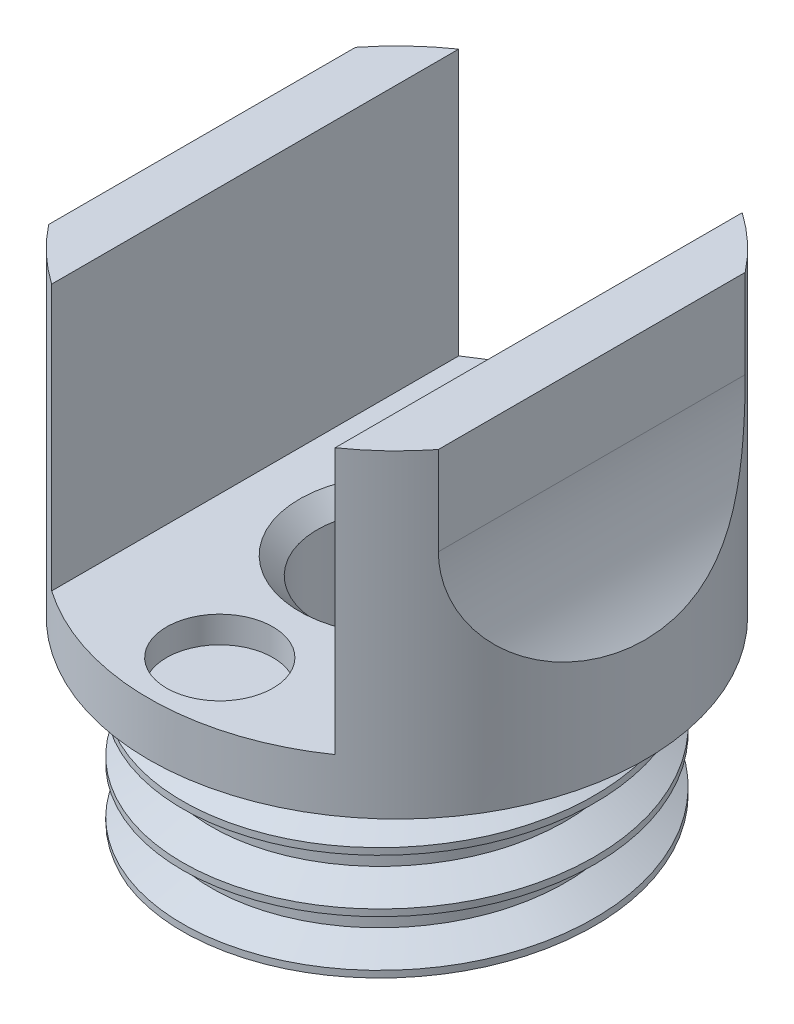
SolidWorks part; units mm, degrees
ref_plane "前视基准面" through (0, 0, 0) normal (0, 0, 1) x (1, 0, 0)
ref_plane "上视基准面" through (0, 0, 0) normal (0, 1, 0) x (1, 0, 0)
ref_plane "右视基准面" through (0, 0, 0) normal (1, 0, 0) x (0, 0, -1)
other "Configuration Table"
sketch "草图1" plane through (0, 0, 0) normal (0, 1, 0) x (1, 0, 0)
  circle A0 centre (0, 0) radius 10
  dimension "D1" = 20
extrude "凸台-拉伸1" add sketch "草图1" along normal blind 10
sketch "草图2" plane through (0, 0, 0) normal (0, -1, 0) x (1, 0, 0)
  circle A0 centre (0, 0) radius 6.5
  circle A1 centre (0, 0) radius 7.5
  dimension "D1" = 13
  dimension "D2" = 15
extrude "切除-拉伸1" cut sketch "草图2" against normal blind 2
chamfer "倒角1" distance 0.5 angle 45 1 edges at (0, 2, -6.5)
chamfer "倒角2" distance 0.5 angle 45 1 edges at (0, 2, -7.5)
sketch "草图3" plane through (0, 0, 0) normal (0, -1, 0) x (1, 0, 0)
  circle A0 centre (0, 0) radius 4.5
  dimension "D1" = 9
extrude "切除-拉伸2" cut sketch "草图3" against normal up to next
sketch "草图4" plane through (0, 10, 0) normal (0, 1, 0) x (1, 0, 0)
  circle A0 centre (0, 0) radius 14
  dimension "D1" = 28
extrude "凸台-拉伸2" add sketch "草图4" along normal blind 3
sketch "草图5" plane through (0, 13, 0) normal (0, 1, 0) x (1, 0, 0)
  line L0 (-8, 12.9311) -> (-8, -12.9311)
  line L1 (-11, 15.9311) -> (11, 15.9311)
  line L2 (-11, 15.9311) -> (-11, -15.9311)
  line L3 (-11, -15.9311) -> (11, -15.9311)
  line L4 (11, 15.9311) -> (11, -15.9311)
  line L5 (-11, 15.9311) -> (11, -15.9311) construction
  line L6 (-11, -15.9311) -> (11, 15.9311) construction
  line L7 (-8, -12.9311) -> (8, -12.9311)
  line L8 (8, 12.9311) -> (8, -12.9311)
  line L9 (-8, 12.9311) -> (8, 12.9311)
  circle A1 centre (0, 0) radius 14
  circle A2 centre (0, 0) radius 14
  point P0 (0, 0)
  circle M5 centre (0, 0) radius 14
  dimension "D2" = 22
  dimension "D1" = 0
  dimension "D3" = 3
extrude "凸台-拉伸3" add sketch "草图5" along normal blind 15 contours L2 L0 M5 | L8 L4 M5 region at (-9.4313, 13, 0) region at (9.4313, 13, 0)
sketch "草图6" plane through (0, 10, 0) normal (0, -1, 0) x (1, 0, 0)
  circle A1 centre (0, 0) radius 4.5
  circle A2 centre (0, 0) radius 4.5
  dimension "D1" = 0
extrude "切除-拉伸3" cut sketch "草图6" against normal up to next
fillet "圆角1" radius 10 2 edges at (-11, 13, 0) (11, 13, 0)
thread "螺纹线1" pitch 3 method extrude trim with start face yes trim with end face yes profile "螺纹线轮廓1" start angle 0, offset 3, length 0, pitch 3, diameter 20
ref_plane "基准面1" through (10, -3, 0) normal (0, 0, 1) x (1, 0, 0)
sketch "螺纹线轮廓1" plane through (10, -3, 0) normal (0, 0, 1) x (1, 0, 0)
  line L0 (0, 0) -> (0, 3) construction
  line L1 (0, 0) -> (1.6238, 0.9375)
  line L2 (1.6238, 0.9375) -> (1.6238, 1.3125)
  line L3 (1.6238, 1.3125) -> (0, 2.25)
  line L4 (1.6238, 1.125) -> (0, 1.125) construction
  line L11 (0, 0) -> (0, 2.25)
  point P2 (0, 0)
  dimension "Pitch" = 3
  dimension "Profile_Angle" = 60
  dimension "Profile_Land" = 0.375
  dimension "Profile_Height" = 1.6238
sketch "草图18" plane through (0, 13, 0) normal (0, 1, 0) x (1, 0, 0)
  circle A0 centre (0, -10) radius 3
  point P2 (0, 0)
  dimension "D1" = 6
  dimension "D2" = 10
extrude "切除-拉伸4" cut sketch "草图18" against normal blind 1.5
chamfer "倒角3" distance 1 angle 45 1 edges at (0, 13, 4.5)
sketch "草图19" plane through (0, 13, 0) normal (0, 1, 0) x (1, 0, 0)
  line L1 (-3, 7.6459) -> (3, 7.6459)
  line L2 (-3, 7.6459) -> (-3, 3.3541)
  line L3 (-3, 3.3541) -> (3, 3.3541)
  line L4 (3, 7.6459) -> (3, 3.3541)
  line L5 (-3, 7.6459) -> (3, 3.3541) construction
  line L6 (-3, 3.3541) -> (3, 7.6459) construction
  circle A0 centre (0, 0) radius 5.5 construction
  circle A1 centre (0, 0) radius 4.5 construction
  circle A2 centre (0, 0) radius 4.5
  point P0 (0, 5.5)
  point P12 (0, 0)
  circle M2 centre (0, 0) radius 5.5
  dimension "D1" = 6
extrude "凸台-拉伸4" add sketch "草图19" against normal up to surface contours A2 L4 L2 M2 region at (0, 13, -4.6568) up to face at (0, 12, 4.5)
fillet "圆角2" radius 1 2 edges at (3, 13, -3.9819) (-3, 13, -3.9819)
